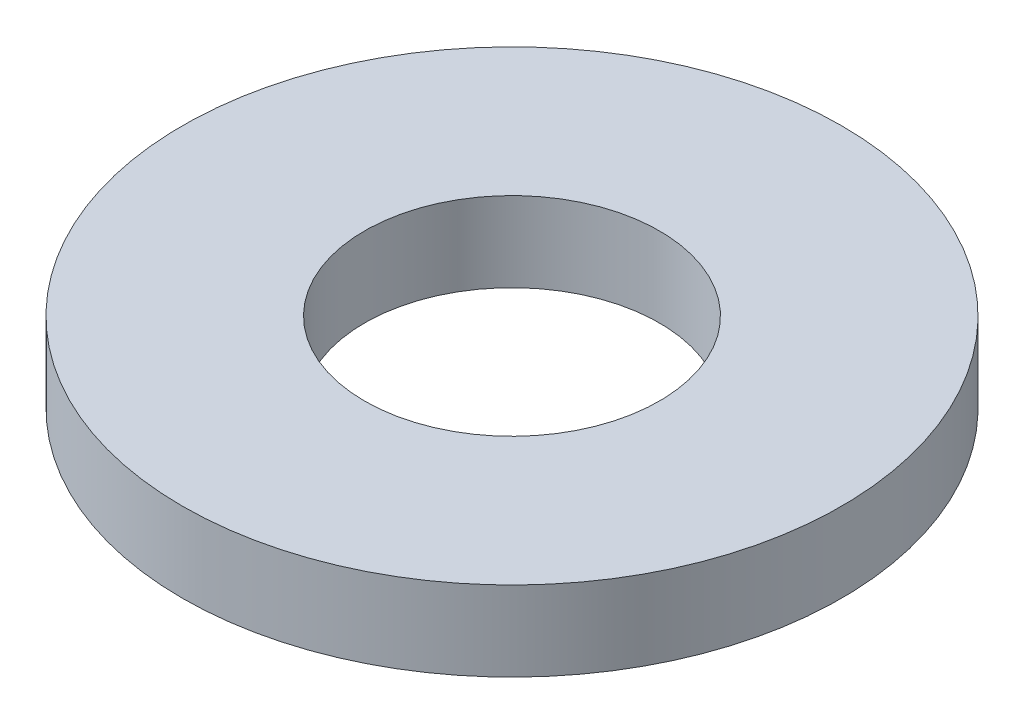
SolidWorks part; units mm, degrees
ref_plane "Front Plane" through (0, 0, 0) normal (0, 0, 1) x (1, 0, 0)
ref_plane "Top Plane" through (0, 0, 0) normal (0, 1, 0) x (1, 0, 0)
ref_plane "Right Plane" through (0, 0, 0) normal (1, 0, 0) x (0, 0, -1)
sketch "Sketch1" plane through (0, 0, 0) normal (0, 1, 0) x (1, 0, 0)
  circle A0 centre (0, 0) radius 95
  dimension "FLANGE_OD" = 190
extrude "Boss-Extrude1" add sketch "Sketch1" along normal blind 23
sketch "Sketch2" plane through (0, 0, 0) normal (0, 1, 0) x (1, 0, 0)
  circle A0 centre (0, 0) radius 42.5
  dimension "BORE_D" = 85
extrude "Cut-Extrude1" cut sketch "Sketch2" along normal through all
sketch "Sketch3" plane through (0, 23, 0) normal (0, 1, 0) x (1, 0, 0)
  circle A0 centre (0, 0) radius 36.8901 construction
  circle A1 centre (-36.8901, 0) radius 5.209
  dimension "BOLT_D" = 10.418
  dimension "BOLT_PCD" = 73.7803
extrude "Cut-Extrude2" cut sketch "Sketch3" against normal blind 22.347 rebuild error yes
pattern_circular "CirPattern1" count 4 over 360 rebuild error yes
